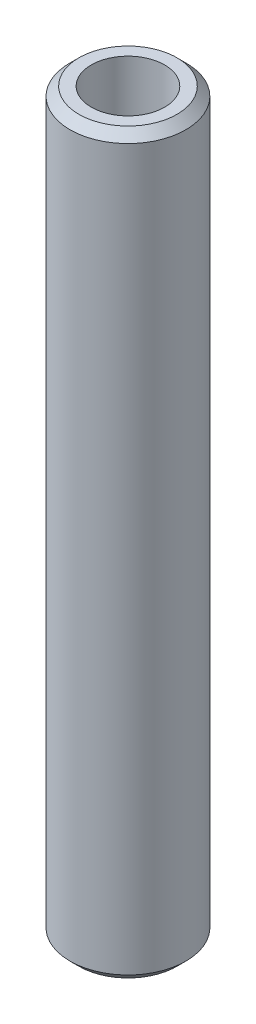
SolidWorks part; units mm, degrees
ref_plane "Front Plane" through (0, 0, 0) normal (0, 0, 1) x (1, 0, 0)
ref_plane "Top Plane" through (0, 0, 0) normal (0, 1, 0) x (1, 0, 0)
ref_plane "Right Plane" through (0, 0, 0) normal (1, 0, 0) x (0, 0, -1)
sketch "Sketch1" plane through (0, 0, 0) normal (0, 1, 0) x (1, 0, 0)
  circle A0 centre (0, 0) radius 35
  dimension "SHAFT_OD" = 70
extrude "Boss-Extrude1" add sketch "Sketch1" along normal blind 445.7273
sketch "Sketch2" plane through (0, 0, 0) normal (0, 1, 0) x (1, 0, 0)
  circle A0 centre (0, 0) radius 22.1492
  dimension "BORE_D" = 44.2983
extrude "Cut-Extrude1" cut sketch "Sketch2" along normal through all
chamfer "Chamfer1" distance 5.3725 angle 45 2 edges at (0, 445.7273, 35) (0, 0, 35)
